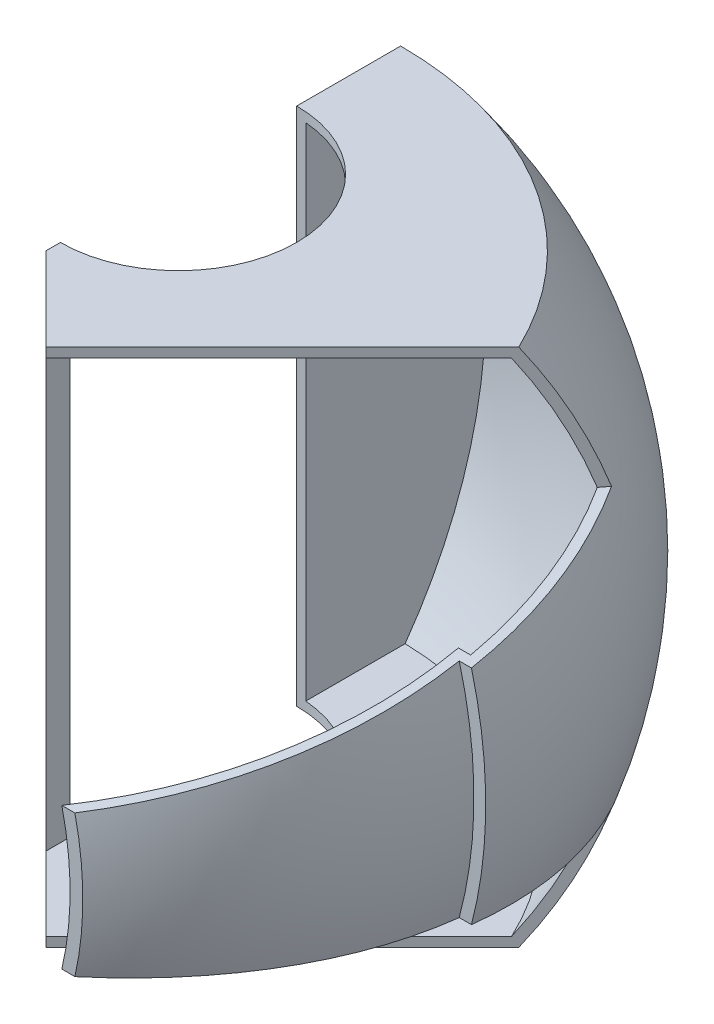
SolidWorks part; units mm, degrees
ref_plane "Front Plane" through (0, 0, 0) normal (0, 0, 1) x (1, 0, 0)
ref_plane "Top Plane" through (0, 0, 0) normal (0, 1, 0) x (1, 0, 0)
ref_plane "Right Plane" through (0, 0, 0) normal (1, 0, 0) x (0, 0, -1)
sketch "Sketch1" plane through (0, 0, 0) normal (1, 0, 0) x (0, 0, -1)
  line L0 (0, 0) -> (-58.4615, 0) construction
  line L1 (0, -55) -> (0, 55)
  line L2 (0, 55) -> (-75, 55)
  line L3 (0, -55) -> (-75, -55)
  arc A0 (-75, 55) -> (-75, -55) centre (0, 0) ccw
  dimension "D1" = 55
  dimension "D2" = 75
revolve "Revolve1" add sketch "Sketch1" angle 180 about L1 region at (0, 0, 43.7882)
sketch "Sketch2" plane through (0, -55, 0) normal (0, -1, 0) x (1, 0, 0)
  line L4 (0, 0) -> (17.6777, 17.6777)
  line L5 (17.6777, 17.6777) -> (97.0571, -61.7018)
  line L10 (0, 0) -> (-129.4347, 0)
  line L11 (-129.4347, 0) -> (-129.4347, 157.408)
  line L12 (-129.4347, 157.408) -> (97.0571, 157.408)
  line L13 (97.0571, 157.408) -> (97.0571, -61.7018)
  dimension "D4" = 25
ref_plane "Plane1" through (100, 0, 0) normal (1, 0, 0) x (0, 0, -1)
extrude "Cut-Extrude3" cut sketch "Sketch2" against normal through all
ref_plane "Plane2" through (100, 0, 0) normal (1, 0, 0) x (0, 0, -1)
sketch "Sketch3" plane through (100, 0, 0) normal (1, 0, 0) x (0, 0, -1)
  line L0 (0, 0) -> (-60, 0) construction
  line L1 (-60, -15) -> (-60, 15)
  line L2 (0, 0) -> (45.6666, 0) construction
  line L3 (45.6666, -30) -> (45.6666, 30)
  line L4 (45.6666, 30) -> (-60, 15)
  line L5 (45.6666, -30) -> (-60, -15)
  dimension "D1" = 60
  dimension "D2" = 15
  dimension "D3" = 30
  dimension "D4" = 60
extrude "Boss-Extrude1" add sketch "Sketch3" against normal up to surface (100 mm away)
sketch "Sketch4" plane through (0, 0, 0) normal (1, 0, 0) x (0, 0, -1)
  line L0 (-74.9933, 55) -> (-155.5635, 55)
  line L1 (-74.9933, -55) -> (-155.5635, -55)
  line L2 (-17.6777, 55) -> (32.3223, 55) construction
  line L3 (0, 0) -> (0, 227.8327) construction
  arc A0 (-74.9933, 55) -> (-74.9933, -55) centre (0, 0) ccw
  arc A1 (-155.5635, 55) -> (-155.5635, -55) centre (0, 0) ccw
  dimension "D1" = 186
  dimension "D2" = 330
revolve "Cut-Revolve1" cut sketch "Sketch4" angle 360 about L3
sketch "Sketch5" plane through (0, -55, 0) normal (0, -1, 0) x (1, 0, 0)
  line L0 (0, 0) -> (74.9935, 74.9935)
  line L1 (74.9935, 74.9935) -> (-71.4355, 74.9935)
  line L2 (-71.4355, 74.9935) -> (-71.4355, 0)
  line L3 (-71.4355, 0) -> (0, 0)
  line L5 (0, 0) -> (17.6777, 17.6777) construction
extrude "Cut-Extrude4" cut sketch "Sketch5" against normal through all
sketch "Sketch6" plane through (0, 0, 0) normal (1, 0, 0) x (0, 0, -1)
  line L0 (-71.8697, 55) -> (-106.6536, 55)
  line L1 (-71.8697, -55) -> (-106.6536, -55)
  line L2 (0, 0) -> (0, 109.7636)
  arc A0 (-71.8697, 55) -> (-71.8697, -55) centre (0, 0) ccw
  arc A1 (-106.6536, 55) -> (-106.6536, -55) centre (0, 0) ccw
  dimension "D1" = 181
  dimension "D2" = 240
revolve "Cut-Revolve2" cut sketch "Sketch6" angle 90 about L2 region at (0, 0, 99.8843)
sketch "Sketch7" plane through (0, -55, 0) normal (0, -1, 0) x (1, 0, 0)
  line L0 (0, 0) -> (0, -28)
  line L1 (0, 0) -> (0, -74.9933) construction
  circle A0 centre (0, -28) radius 25
  line M1 (0, 0) -> (0, -74.9933)
  dimension "D2" = 50
  dimension "D1" = 28
extrude "Cut-Extrude5" cut sketch "Sketch7" against normal through all contours A0 L0 M1 | L0 A0 M1 region at (10.6103, -55, -28) region at (-10.6103, -55, -28)
shell "Shell1" thickness 2 removed face at (12.5, 0, -28) removed face at (67.8381, 21.2275, 16.1305) removed face at (45.3122, 40.2679, -9.9568) removed face at (45.3122, -40.2679, -9.9568) removed face at (67.8381, -21.2275, 16.1305) removed face at (23.8388, 0, 23.8388) removed face at (63.4554, 0, 60)
